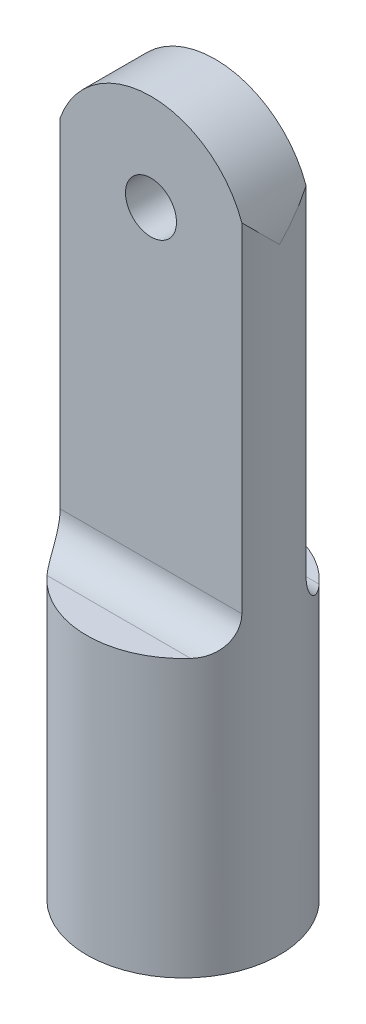
SolidWorks part; units mm, degrees
ref_plane "Front Plane" through (0, 0, 0) normal (0, 0, 1) x (1, 0, 0)
ref_plane "Top Plane" through (0, 0, 0) normal (0, 1, 0) x (1, 0, 0)
ref_plane "Right Plane" through (0, 0, 0) normal (1, 0, 0) x (0, 0, -1)
sketch "Sketch7" plane through (0, 0, 0) normal (0, 1, 0) x (1, 0, 0)
  circle A0 centre (0, 0) radius 6
  dimension "D1" = 12
extrude "Boss-Extrude2" add sketch "Sketch7" along normal blind 45
sketch "Sketch8" plane through (0, 0, 0) normal (0, 1, 0) x (1, 0, 0)
  circle A0 centre (0, 0) radius 1.65
  dimension "D1" = 3.3
extrude "Cut-Extrude2" cut sketch "Sketch8" along normal blind 10
thread "Thread2" pitch 1 method cut profile "Thread Profile2" start angle 0, offset 1, length 10, pitch 1, diameter 3.3
ref_plane "Plane2" through (1.65, -1, 0) normal (0, 0, 1) x (1, 0, 0)
sketch "Thread Profile2" plane through (1.65, -1, 0) normal (0, 0, 1) x (1, 0, 0)
  line L0 (0, 0) -> (0, 1) construction
  line L1 (0, 0) -> (0.5413, 0.3125)
  line L2 (0.5413, 0.3125) -> (0.5413, 0.4375)
  line L3 (0.5413, 0.4375) -> (0, 0.75)
  line L4 (0.5413, 0.375) -> (0, 0.375) construction
  line L11 (0, 0) -> (0, 0.75)
  point P2 (0, 0)
  dimension "Pitch" = 1
  dimension "Profile_Angle" = 60
  dimension "Profile_Land" = 0.125
  dimension "Profile_Height" = 0.5413
sketch "Sketch11" plane through (0, 0, 0) normal (0, -1, 0) x (-1, 0, 0)
  circle A0 centre (0, 0) radius 3
  dimension "D1" = 6
extrude "Cut-Extrude3" cut sketch "Sketch11" against normal blind 20 draft 45
sketch "Sketch12" plane through (0, 0, 0) normal (0, 0, 1) x (1, 0, 0)
  line L0 (0, 0) -> (0, 38.3) construction
  line L1 (1.65, 0) -> (-1.65, 0) construction
  line L2 (-6, 38.3) -> (-6, 45)
  line L3 (-6, 45) -> (0, 45)
  line L4 (0, 45) -> (6, 45)
  line L5 (6, 38.3) -> (6, 45)
  line L6 (-6, 45) -> (-6, 0) construction
  line L7 (6, 45) -> (-6, 45) construction
  circle A0 centre (0, 38.3) radius 1.5875
  arc A1 (6, 38.3) -> (-6, 38.3) centre (0, 38.3) ccw
  dimension "D2" = 3.175
  dimension "D1" = 38.3
extrude "Cut-Extrude4" cut sketch "Sketch12" against normal through all and the other way through all contours A1 L3 L2 | A1 L5 L4 | A0 | L2 L3 L4 L5 A1 region at (-5.8626, 41.65, 0)
sketch "Sketch13" plane through (0, 0, 0) normal (1, 0, 0) x (0, 0, -1)
  line L0 (0, 0) -> (0, 96.5632) construction
  line L1 (-2, 17.2252) -> (-2, 55.0508)
  line L2 (-2, 55.0508) -> (-6, 55.0508)
  line L3 (-6, 36.7125) -> (-6, 0) construction
  line L4 (-6, 55.0508) -> (-6, 17.2252)
  line L6 (-6, 17.2252) -> (-2, 17.2252)
  line L7 (6, 17.2252) -> (2, 17.2252)
  line L8 (6, 55.0508) -> (6, 17.2252)
  line L9 (2, 55.0508) -> (6, 55.0508)
  line L10 (2, 17.2252) -> (2, 55.0508)
  dimension "D1" = 2
extrude "Cut-Extrude5" cut sketch "Sketch13" against normal through all and the other way through all contours L10 L9 L8 L7 | L1 L2 L4 L6
fillet "Fillet1" radius 2 2 edges at (0, 17.2252, 2) (0, 17.2252, -2)
